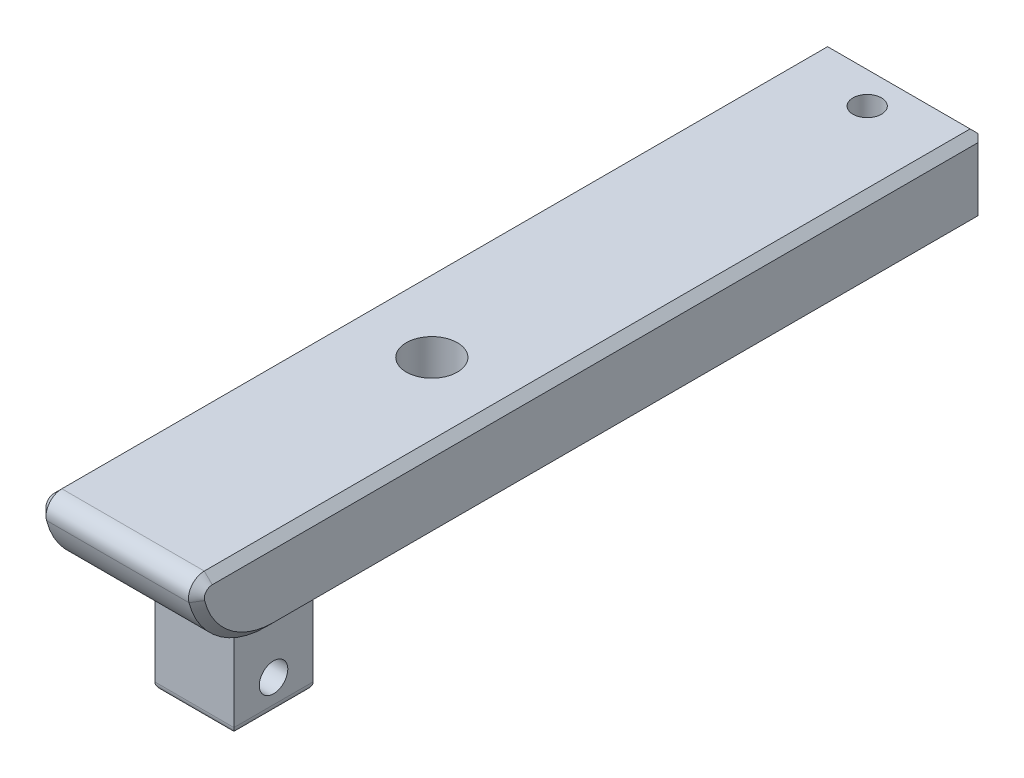
SolidWorks part; units mm, degrees
ref_plane "Front Plane" through (0, 0, 0) normal (0, 0, 1) x (1, 0, 0)
ref_plane "Top Plane" through (0, 0, 0) normal (0, 1, 0) x (1, 0, 0)
ref_plane "Right Plane" through (0, 0, 0) normal (1, 0, 0) x (0, 0, -1)
sketch "Sketch1" plane through (0, 0, 0) normal (0, 1, 0) x (1, 0, 0)
  line L1 (0, 0) -> (20, 0)
  line L2 (0, 0) -> (0, 100)
  line L3 (0, 100) -> (20, 100)
  line L4 (20, 0) -> (20, 100)
  dimension "D1" = 20
  dimension "D2" = 100
extrude "Boss-Extrude1" add sketch "Sketch1" along normal blind 10
hole_wizard "M3 Clearance Hole1" positions "3DSketch1" profile "Sketch2" hole size "M3" standard "ANSI Metric" end condition through all
sketch3d "3DSketch1"
  line L0 (20, 0, -100) -> (0, 0, -100) construction
  line L1 (20, 0, 0) -> (20, 0, -100) construction
  point P0 (10, 0, -95)
  dimension "D1" = 5
  dimension "D2" = 10
sketch "Sketch2" plane through (10, 0, -95) normal (1, 0, 0) x (0, 0, -1)
  line L0 (0, 0) -> (0, 10)
  line L1 (0, 10) -> (1.8, 10)
  line L2 (1.8, 10) -> (1.8, 0)
  line L5 (1.8, 0) -> (0, 0)
  line L11 (0, -6.35) -> (0, 107.95) construction
  dimension "Thru Hole Dia." = 3.6
  dimension "Thru Hole Depth" = 10
sketch "Sketch3" plane through (0, 0, 0) normal (0, -1, 0) x (1, 0, 0)
  line L0 (0, -100) -> (0, 0) construction
  line L1 (5, -10) -> (15, -10)
  line L2 (5, -10) -> (5, -20)
  line L3 (5, -20) -> (15, -20)
  line L4 (15, -10) -> (15, -20)
  line L5 (0, 0) -> (20, 0) construction
  dimension "D1" = 10
  dimension "D2" = 5
  dimension "D3" = 10
  dimension "D4" = 10
extrude "Boss-Extrude2" add sketch "Sketch3" along normal blind 14
hole_wizard "M3 Clearance Hole5" positions "3DSketch5" profile "Sketch7" hole size "M3" standard "ANSI Metric" end condition through all
sketch3d "3DSketch5"
  line L0 (5, -14, -10) -> (5, -14, -20) construction
  line L1 (5, -14, -20) -> (5, 0, -20) construction
  point P0 (5, -10, -15)
  dimension "D1" = 4
  dimension "D2" = 5
sketch "Sketch7" plane through (5, -10, -15) normal (0, 1, 0) x (0, 0, 1)
  line L0 (0, 0) -> (0, 15)
  line L1 (0, 15) -> (1.8, 15)
  line L2 (1.8, 15) -> (1.8, 0)
  line L5 (1.8, 0) -> (0, 0)
  line L11 (0, -6.35) -> (0, 107.95) construction
  dimension "Thru Hole Dia." = 3.6
  dimension "Thru Hole Depth" = 15
hole_wizard "1/4 (0.254) Diameter Hole1" positions "3DSketch6" profile "Sketch8" hole size "1/4" standard "ANSI Inch" end condition up to next
sketch3d "3DSketch6"
  line L0 (20, 0, -100) -> (0, 0, -100) construction
  line L1 (20, 0, 0) -> (20, 0, -100) construction
  point P0 (10, 0, -40)
  dimension "D1" = 60
  dimension "D2" = 10
sketch "Sketch8" plane through (10, 0, -40) normal (1, 0, 0) x (0, 0, -1)
  line L0 (0, 0) -> (0, 10)
  line L1 (0, 10) -> (3.2258, 10)
  line L2 (3.2258, 10) -> (3.2258, 0)
  line L5 (3.2258, 0) -> (0, 0)
  line L11 (0, -6.35) -> (0, 107.95) construction
  dimension "Thru Hole Dia." = 6.4516
  dimension "Thru Hole Depth" = 10
fillet "Fillet1" radius 10 1 edges at (10, 0, 0)
fillet "Fillet2" radius 2 1 edges at (10, 10, 0)
chamfer "Chamfer1" distance 1 angle 45 10 edges at (20, 5, -100) (20, 0, -55) (20, 2.0943, -3.8763) (20, 9.2247, -0.6729) (20, 10, -51.127) (0, 0, -55) (0, 5, -100) (0, 10, -51.127) (0, 9.2247, -0.6729) (0, 2.0943, -3.8763)
fillet "Fillet3" radius 1 4 edges at (10, -14, -20) (5, -14, -15) (10, -14, -10) (15, -14, -15)
chamfer "Chamfer2" distance 1 angle 45 2 edges at (10, 10, -100) (10, 0, -100)
